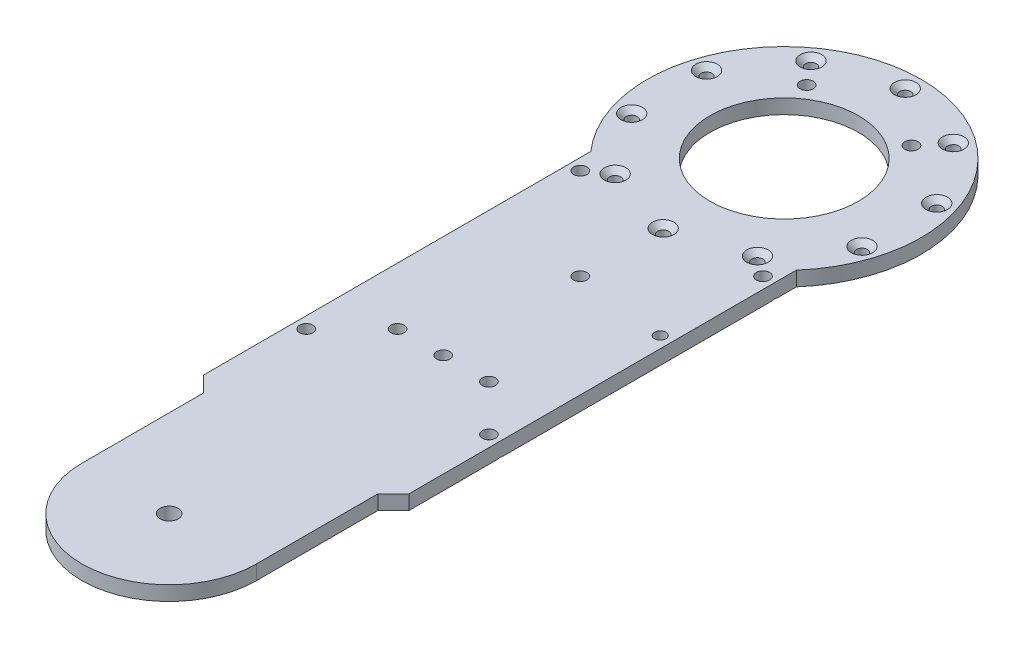
SolidWorks part; units mm, degrees
material "6061 Alloy"
ref_plane "Front Plane" through (0, 0, 0) normal (0, 0, 1) x (1, 0, 0)
ref_plane "Top Plane" through (0, 0, 0) normal (0, 1, 0) x (1, 0, 0)
ref_plane "Right Plane" through (0, 0, 0) normal (1, 0, 0) x (0, 0, -1)
sketch "Sketch1" plane through (0, 0, 0) normal (0, 1, 0) x (1, 0, 0)
  line L0 (0, 0) -> (0, -307.5) construction
  line L1 (-45, 0) -> (45, 0) construction
  line L2 (-45, 0) -> (-45, -219.3) construction
  line L3 (-45, -219.3) -> (-38.2, -219.3)
  line L4 (-38.2, -219.3) -> (-38.2, -269.3)
  line L5 (38.2, -269.3) -> (38.2, -219.3)
  line L6 (38.2, -219.3) -> (45, -219.3)
  line L7 (45, -219.3) -> (45, 0) construction
  line L8 (-45, -219.3) -> (-45, -39.6863)
  line L9 (45, -219.3) -> (45, -39.6863)
  arc A0 (45, -39.6863) -> (-45, -39.6863) centre (0, 0) ccw
  circle A1 centre (0, 0) radius 45 construction
  circle A2 centre (0, 0) radius 40 construction
  arc A3 (-38.2, -269.3) -> (38.2, -269.3) centre (0, -269.3) ccw
  point P1 (0, 60)
  dimension "D1" = 120
  dimension "D2" = 38.2
  dimension "D7" = 90
  dimension "D8" = 80
  dimension "D3" = 219.3
  dimension "D4" = 50
  dimension "D5" = 6.8
  dimension "D6" = 307.5
  dimension "D9" = 367.5
extrude "Boss-Extrude1" add sketch "Sketch1" along normal blind 6.35
sketch "Sketch2" plane through (0, 6.35, 0) normal (0, 1, 0) x (1, 0, 0)
  line L0 (-40, 0) -> (-40, -49.3) construction
  line L1 (-40, -49.3) -> (-40, -169.3) construction
  line L2 (0, -89.3) -> (0, -149.3) construction
  line L3 (40, -49.3) -> (40, -169.3) construction
  line L4 (40, 0) -> (40, -49.3) construction
  line L5 (0, 0) -> (0, -89.3) construction
  line L8 (0, -149.3) -> (-20, -149.3) construction
  line L9 (0, -149.3) -> (20, -149.3) construction
  circle A0 centre (0, 0) radius 53 construction
  circle A1 centre (0, 53) radius 2
  circle A2 centre (31.1526, 42.8779) radius 2
  circle A3 centre (50.406, 16.3779) radius 2
  circle A4 centre (50.406, -16.3779) radius 2
  circle A5 centre (31.1526, -42.8779) radius 2
  circle A6 centre (0, -53) radius 2
  circle A7 centre (-31.1526, -42.8779) radius 2
  circle A8 centre (-50.406, -16.3779) radius 2
  circle A9 centre (-50.406, 16.3779) radius 2
  circle A10 centre (-31.1526, 42.8779) radius 2
  circle A11 centre (0, 0) radius 32.5
  circle A12 centre (0, -269.3) radius 4
  circle A13 centre (0, 0) radius 45 construction
  circle A14 centre (0, 0) radius 40 construction
  circle A15 centre (-40, -169.3) radius 5 construction
  circle A16 centre (-40, -169.3) radius 2.5
  circle A17 centre (-40, -49.3) radius 5 construction
  circle A18 centre (-40, -49.3) radius 2.5
  circle A19 centre (40, -169.3) radius 2.5
  circle A20 centre (40, -169.3) radius 5 construction
  circle A21 centre (40, -49.3) radius 2.5
  circle A22 centre (40, -49.3) radius 5 construction
  circle A23 centre (0, -89.3) radius 2.5
  circle A26 centre (-20, -149.3) radius 2.5
  circle A27 centre (0, -149.3) radius 2.5
  circle A28 centre (20, -149.3) radius 2.5
  arc A29 (0, 40) -> (22.9431, 32.7661) centre (0, 0) cw construction
  arc A30 (0, 40) -> (-22.9431, 32.7661) centre (0, 0) ccw construction
  circle A31 centre (-22.9431, 32.7661) radius 2.5
  circle A32 centre (22.9431, 32.7661) radius 2.5
  circle A33 centre (40, -94.3) radius 2.5
  point P24 (0, 0)
  dimension "D1" = 10
  dimension "D2" = 4
  dimension "D3" = 65
  dimension "D4" = 80
  dimension "D5" = 90
  dimension "D8" = 10
  dimension "D9" = 10
  dimension "D10" = 5
  dimension "D14" = 35
  dimension "D15" = 5
  dimension "D18" = 45
  dimension "D6" = 49.3
  dimension "D7" = 120
  dimension "D11" = 89.3
  dimension "D12" = 60
  dimension "D13" = 20
  dimension "D16" = 49.3
  dimension "D17" = 120
extrude "Cut-Extrude1" cut sketch "Sketch2" against normal through all
chamfer "Chamfer1" distance 10 angle 45 2 edges at (45, 3.175, 219.3) (-45, 3.175, 219.3)
hole_wizard "CSK for M4 Oval Head Machine Screw1" positions "3DSketch1" profile "Sketch3" countersink size "M4" standard "ANSI Metric" end condition through all
sketch3d "3DSketch1"
  line L0 (-50.406, 0, 16.3779) -> (-50.406, 6.35, 16.3779) construction
  line L1 (-50.406, 0, -16.3779) -> (-50.406, 6.35, -16.3779) construction
  line L2 (-31.1526, 0, -42.8779) -> (-31.1526, 6.35, -42.8779) construction
  line L3 (0, 0, -53) -> (0, 6.35, -53) construction
  line L4 (31.1526, 0, -42.8779) -> (31.1526, 6.35, -42.8779) construction
  line L5 (50.406, 0, -16.3779) -> (50.406, 6.35, -16.3779) construction
  line L6 (50.406, 0, 16.3779) -> (50.406, 6.35, 16.3779) construction
  line L7 (31.1526, 0, 42.8779) -> (31.1526, 6.35, 42.8779) construction
  line L8 (0, 0, 53) -> (0, 6.35, 53) construction
  line L9 (-31.1526, 0, 42.8779) -> (-31.1526, 6.35, 42.8779) construction
  point P0 (-50.406, 6.35, 16.3779)
  point P4 (-50.406, 6.35, -16.3779)
  point P8 (-31.1526, 6.35, -42.8779)
  point P12 (0, 6.35, -53)
  point P16 (31.1526, 6.35, -42.8779)
  point P20 (50.406, 6.35, -16.3779)
  point P24 (50.406, 6.35, 16.3779)
  point P28 (31.1526, 6.35, 42.8779)
  point P32 (0, 6.35, 53)
  point P36 (-31.1526, 6.35, 42.8779)
sketch "Sketch3" plane through (-50.406, 6.35, 16.3779) normal (1, 0, 0) x (0, 0, 1)
  line L0 (0, 0) -> (0, 6.35)
  line L1 (0, 6.35) -> (2.4, 6.35)
  line L2 (2.4, 6.35) -> (2.4, 2.3)
  line L3 (2.4, 2.3) -> (4.7, 0)
  line L5 (4.7, 0) -> (0, 0)
  line L6 (-2.4, 2.3) -> (-4.7, 0) construction
  line L11 (0, -6.35) -> (0, 107.95) construction
  dimension "Thru Hole Dia." = 4.8
  dimension "Thru Hole Depth" = 6.35
  dimension "Near C'Sink Dia." = 9.4
  dimension "Near C'Sink Angle" = 90
hole_wizard "CSK for M5 Oval Head Machine Screw1" positions "3DSketch2" profile "Sketch4" countersink size "M5" standard "ANSI Metric"
sketch3d "3DSketch2"
  line L0 (22.9431, 0, -32.7661) -> (22.9431, 6.35, -32.7661) construction
  line L1 (-22.9431, 0, -32.7661) -> (-22.9431, 6.35, -32.7661) construction
  line L3 (0, 0, 89.3) -> (0, 6.35, 89.3) construction
  line L5 (40, 0, 49.3) -> (40, 6.35, 49.3) construction
  line L6 (-40, 0, 49.3) -> (-40, 6.35, 49.3) construction
  line L7 (-40, 0, 169.3) -> (-40, 6.35, 169.3) construction
  line L8 (40, 0, 169.3) -> (40, 6.35, 169.3) construction
  line L9 (20, 0, 149.3) -> (20, 6.35, 149.3) construction
  line L10 (0, 0, 149.3) -> (0, 6.35, 149.3) construction
  line L11 (-20, 0, 149.3) -> (-20, 6.35, 149.3) construction
  point P0 (22.9431, 0, -32.7661)
  point P4 (-22.9431, 0, -32.7661)
  point P12 (0, 0, 89.3)
  point P20 (40, 0, 49.3)
  point P24 (-40, 0, 49.3)
  point P28 (-40, 0, 169.3)
  point P32 (40, 0, 169.3)
  point P36 (20, 0, 149.3)
  point P40 (0, 0, 149.3)
  point P44 (-20.8462, 0, 150.1789)
  point P46 (-20, 0, 149.3)
sketch "Sketch4" plane through (22.9431, 0, -32.7661) normal (1, 0, 0) x (0, 0, -1)
  line L0 (0, 0) -> (0, 6.35)
  line L1 (0, 6.35) -> (2.9, 6.35)
  line L2 (2.9, 6.35) -> (2.9, 2.3)
  line L3 (2.9, 2.3) -> (5.2, 0)
  line L5 (5.2, 0) -> (0, 0)
  line L6 (-2.9, 2.3) -> (-5.2, 0) construction
  line L11 (0, -6.35) -> (0, 107.95) construction
  dimension "Thru Hole Dia." = 5.8
  dimension "Thru Hole Depth" = 6.35
  dimension "Near C'Sink Dia." = 10.4
  dimension "Near C'Sink Angle" = 90
